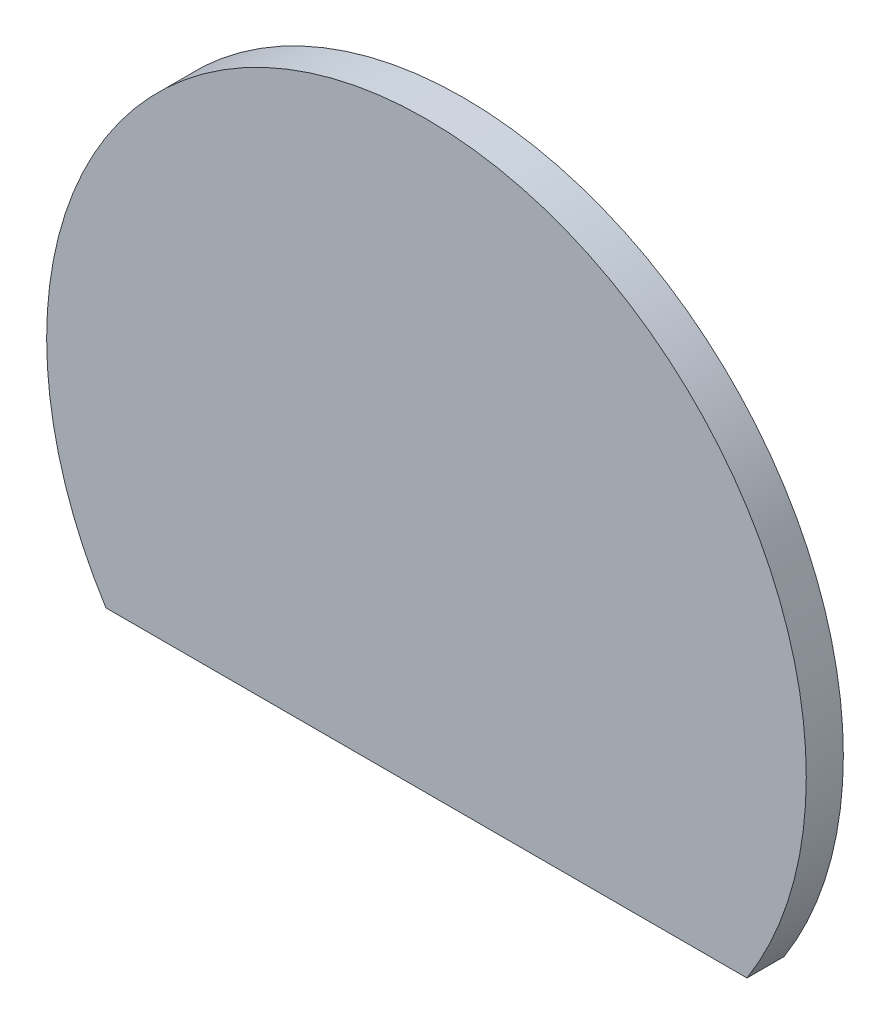
SolidWorks part; units mm, degrees
ref_plane "Front Plane" through (0, 0, 0) normal (0, 0, 1) x (1, 0, 0)
ref_plane "Top Plane" through (0, 0, 0) normal (0, 1, 0) x (1, 0, 0)
ref_plane "Right Plane" through (0, 0, 0) normal (1, 0, 0) x (0, 0, -1)
sketch "Sketch1" plane through (0, 0, 0) normal (0, 0, 1) x (1, 0, 0)
  line L0 (-8.6494, -5.5) -> (8.6494, -5.5)
  arc A0 (8.6494, -5.5) -> (-8.6494, -5.5) centre (0, 0) ccw
  circle A1 centre (0, 0) radius 4.5
  circle A2 centre (0, 0) radius 5.5
  dimension "D1" = 20.5
  dimension "D2" = 9
  dimension "D3" = 1
extrude "Boss-Extrude1" add sketch "Sketch1" along normal blind 1 contours L0 A2 A0 | A1 | A2 A1 region at (-3.7791, 3.7791, 0) region at (0, 9.9915, 0) region at (0, 0, 0)
extrude "Boss-Extrude2" add sketch "Sketch1<4>" against normal blind 2 contours A1 | A2
sketch "Sketch1<4>" plane through (0, 0, 0) normal (0, 0, 1) x (1, 0, 0) same geometry as "Sketch1"
